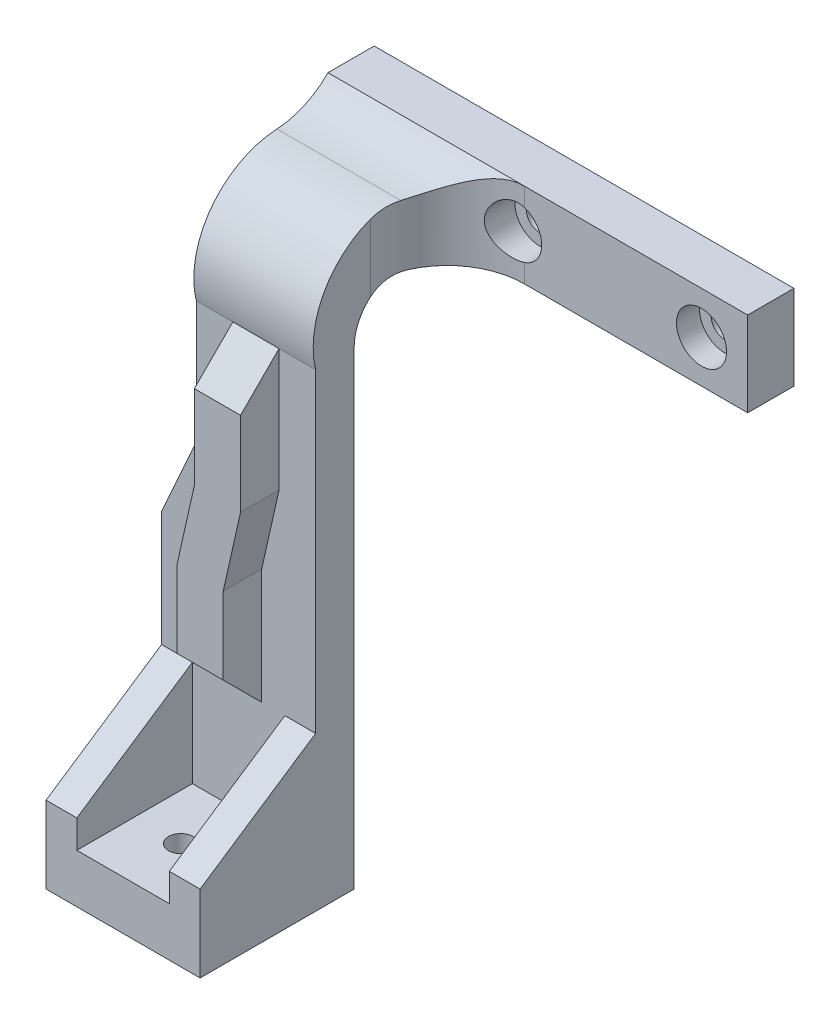
SolidWorks part; units mm, degrees
ref_plane "Plano frontal" through (0, 0, 0) normal (0, 0, 1) x (1, 0, 0)
ref_plane "Plano superior" through (0, 0, 0) normal (0, 1, 0) x (1, 0, 0)
ref_plane "Plano direito" through (0, 0, 0) normal (1, 0, 0) x (0, 0, -1)
sketch "Esboço2" plane through (0, 0, 0) normal (0, 0, 1) x (1, 0, 0)
  line L0 (0, 0) -> (0, -60.9)
  line L1 (0, -60.9) -> (-20, -60.9)
  line L2 (-20, -60.9) -> (-20, -25.9)
  line L3 (-20, -25.9) -> (-15.5, -15.9)
  line L4 (-15.5, -15.9) -> (-15.5, 0)
  line L5 (-15.5, 0) -> (0, 0)
  dimension "D1" = 15.5
  dimension "D2" = 60.9
  dimension "D3" = 35
  dimension "D4" = 15.9
  dimension "D5" = 20
extrude "Ressalto-extrusão1" add sketch "Esboço2" along normal blind 5
sketch "Esboço3" plane through (0, 0, 0) normal (1, 0, 0) x (0, 0, -1)
  line L0 (-5, 0) -> (0, 0)
  line L1 (6.1023, 6.1) -> (6.1023, 14.1) construction
  line L2 (6.1023, 6.1) -> (30.1023, 6.1)
  line L3 (6.1023, 14.1) -> (50.2046, 14.1)
  line L4 (45.2046, -9.0023) -> (45.2046, -60.9)
  line L5 (45.2046, -60.9) -> (50.2046, -60.9)
  line L6 (50.2046, -60.9) -> (50.2046, 14.1)
  arc A0 (6.1023, 6.1) -> (0, 0) centre (6.1023, -0.0023) ccw
  arc A1 (6.1023, 14.1) -> (-5, 0) centre (6.1018, 2.6794) ccw
  arc A2 (45.2046, -9.0029) -> (30.1016, 6.1) centre (30.1016, -9.0029) ccw
extrude "Ressalto-extrusão2" add sketch "Esboço3" against normal up to surface (15.5 mm away) up to face at (-15.5, -7.95, 2.5)
sketch "Esboço4" plane through (-15.5, 0, 0) normal (-1, 0, 0) x (0, 0, 1)
  line L0 (-50.2046, -60.9) -> (-50.2046, -40.9)
  line L2 (-50.2046, -40.9) -> (-65.2046, -50.9)
  line L3 (-65.2046, -50.9) -> (-65.2046, -60.9)
  line L4 (-65.2046, -60.9) -> (-65.2046, -50.9) construction
  line L5 (-65.2046, -60.9) -> (-50.2046, -40.9) construction
  line L6 (-65.2046, -60.9) -> (-50.2046, -60.9)
  line L13 (-50.2046, 14.1) -> (-50.2046, -60.9) construction
  dimension "D1" = 20
extrude "Ressalto-extrusão3" add sketch "Esboço4" against normal up to surface (15.5 mm away) up to face at (0, -18.647, -20.1425)
sketch "Esboço5" plane through (-20, 0, 0) normal (-1, 0, 0) x (0, 0, 1)
  line L0 (5, -60.9) -> (20, -60.9)
  line L1 (20, -60.9) -> (20, -50.9)
  line L2 (20, -50.9) -> (5, -40.9)
  line L3 (5, -25.9) -> (5, -60.9) construction
  line L4 (5, -40.9) -> (20, -50.9) construction
  line L5 (5, -40.9) -> (5, -60.9)
extrude "Ressalto-extrusão4" add sketch "Esboço5" against normal up to surface (20 mm away) up to face at (0, -22.8397, -27.0751)
sketch "Esboço6" plane through (-15.5, 0, 0) normal (-1, 0, 0) x (0, 0, 1)
  line L5 (-50.2046, -44.0023) -> (-45.2046, -44.0023)
  line L6 (-50.2046, -44.0023) -> (-50.2046, -60.9)
  line L7 (-50.2046, -60.9) -> (-45.2046, -60.9)
  line L8 (-45.2046, -44.0023) -> (-45.2046, -60.9)
extrude "Ressalto-extrusão5" add sketch "Esboço6" along normal blind 23.2
sketch "Esboço7" plane through (0, 0, -45.2046) normal (0, 0, 1) x (1, 0, 0)
  line L0 (-25.2, -44.0023) -> (-25.2, -60.9) construction
  line L1 (-38.7, -44.0023) -> (-25.2, -44.0023)
  line L2 (-38.7, -44.0023) -> (-38.7, -60.9)
  line L3 (-38.7, -60.9) -> (-25.2, -60.9)
  line L4 (-25.2, -44.0023) -> (-25.2, -60.9)
  line L5 (-38.7, -60.9) -> (0, -60.9) construction
extrude "Ressalto-extrusão6" add sketch "Esboço7" along normal blind 8
sketch "Esboço8" plane through (-15.5, 0, 0) normal (-1, 0, 0) x (0, 0, 1)
  line L1 (-45.2046, -9.0023) -> (-47.2046, -9.0023)
  line L2 (-45.2046, -9.0023) -> (-45.2046, -15.5904)
  line L3 (-45.2046, -15.5904) -> (-47.2046, -15.5904)
  line L4 (-47.2046, -9.0023) -> (-47.2046, -15.5904)
extrude "Corte-extrusão1" cut sketch "Esboço8" against normal through all
chamfer "Chanfro2" distance 9 angle 45 1 edges at (-15.5, -44.0023, -47.7046)
sketch "Esboço10" plane through (-15.5, 0, 0) normal (-1, 0, 0) x (0, 0, 1)
  line L0 (-50.2046, -40.9) -> (-50.2046, -60.9)
  line L1 (-50.2046, -60.9) -> (-65.2046, -60.9)
  line L2 (-65.2046, -60.9) -> (-65.2046, -50.9)
  line L3 (-65.2046, -50.9) -> (-50.2046, -40.9)
  dimension "D1" = 20
extrude "Ressalto-extrusão8" add sketch "Esboço10" along normal blind 4.5
sketch "Esboço9" plane through (0, -60.9, 0) normal (0, -1, 0) x (1, 0, 0)
  line L0 (-38.7, -50.2046) -> (-38.7, -53.2046)
  line L1 (-38.7, -53.2046) -> (-20, -59.2046)
  line L5 (-20, -65.2046) -> (-20, -50.2046) construction
  line L6 (-20, -59.2046) -> (-38.7, -53.2046) construction
  line L7 (-38.7, -50.2046) -> (-20, -50.2046)
  line L8 (-20, -50.2046) -> (-20, -59.2046)
extrude "Ressalto-extrusão7" add sketch "Esboço9" against normal blind 6 from offset 5.5 offset against normal yes
sketch "Esboço11" plane through (0, 0, 5) normal (0, 0, 1) x (1, 0, 0)
  line L0 (0, -40.9) -> (-20, -40.9) construction
  line L1 (-16, -40.9) -> (-4, -40.9)
  line L2 (-16, -40.9) -> (-16, -54.5408)
  line L3 (-16, -54.5408) -> (-4, -54.5408)
  line L4 (-4, -40.9) -> (-4, -54.5408)
  line L5 (-16, -50.9) -> (-16, -40.9) construction
extrude "Corte-extrusão2" cut sketch "Esboço11" along normal up to surface up to face at (-10, -45.9, 12.5)
sketch "Esboço13" plane through (0, -60.9, 0) normal (0, -1, 0) x (1, 0, 0)
  line L0 (0, 20) -> (-20, 20) construction
  line L1 (0, -65.2046) -> (-20, -65.2046) construction
  line L2 (0, -45.2046) -> (0, -65.2046) construction
  circle A0 centre (-10, 12.5) radius 1.6
  circle A1 centre (-9.7, -57.7046) radius 1.6
  point P5 (-10, 20)
  dimension "D1" = 3.2
  dimension "D3" = 3.2
  dimension "D2" = 7.5
  dimension "D4" = 9.7
  dimension "D5" = 7.5
extrude "Corte-extrusão4" cut sketch "Esboço13" against normal up to next
sketch "Esboço14" plane through (0, 0, 5) normal (0, 0, 1) x (1, 0, 0)
  line L0 (0, 0) -> (-15.5, 0) construction
  line L1 (-10.75, 0) -> (-4.75, 0)
  line L2 (-10.75, 0) -> (-10.75, -15.9)
  line L4 (-4.75, 0) -> (-4.75, -15.9)
  line L6 (-13, -40.9) -> (-7, -40.9)
  line L7 (-16, -54.5408) -> (-4, -54.5408) construction
  line L8 (0, -40.9) -> (-4, -40.9) construction
  line L9 (-10.75, -15.9) -> (-13, -25.9)
  line L10 (-13, -25.9) -> (-13, -40.9)
  line L11 (-7, -40.9) -> (-7, -25.9)
  line L12 (-7, -25.9) -> (-4.75, -15.9)
  point P6 (-7.75, 0)
  point P7 (-7.75, 0)
  point P11 (-10, -54.5408)
  point P14 (-10, -40.9)
  dimension "D1" = 6
  dimension "D2" = 6
extrude "Ressalto-extrusão9" add sketch "Esboço14" along normal blind 5
sketch "Esboço16" plane through (0, 0, -50.2046) normal (0, 0, -1) x (-1, 0, 0)
  line L0 (0, -40.9) -> (15.5, -40.9) construction
  line L1 (15.5009, -54.5427) -> (4, -54.5427)
  line L2 (15.5009, -54.5427) -> (15.5009, -40.9)
  line L3 (15.5009, -40.9) -> (4, -40.9)
  line L4 (4, -54.5427) -> (4, -40.9)
  line L5 (0, -50.9) -> (4, -40.9) construction
extrude "Corte-extrusão5" cut sketch "Esboço16" along normal through all
sketch "Esboço17" plane through (0, 0, -50.2046) normal (0, 0, -1) x (-1, 0, 0)
  line L0 (6.7505, -40.9) -> (12.7505, -40.9)
  line L2 (12.7505, -40.9) -> (12.7505, 8.1)
  line L3 (12.7505, 8.1) -> (6.7505, 8.1)
  line L4 (6.7505, 8.1) -> (6.7505, -40.9)
  line L5 (4, -54.5427) -> (15.5009, -54.5427) construction
  line L6 (0, -40.9) -> (4, -40.9) construction
  line L7 (15.5, 14.1) -> (0, 14.1) construction
  point P6 (9.7505, -54.5427)
  point P7 (9.7505, -40.9)
  dimension "D1" = 6
  dimension "D2" = 6
extrude "Ressalto-extrusão11" add sketch "Esboço17" along normal blind 5
chamfer "Chanfro3" distance 5 angle 45 4 edges at (-9.7505, -40.9, -55.2046) (-9.7505, 8.1, -55.2046) (-10, -40.9, 10) (-7.75, 0, 10)
sketch "Esboço18" plane through (0, 0, 0) normal (1, 0, 0) x (0, 0, -1)
  line L5 (6.1023, 6.1) -> (30.1023, 6.1) construction
  line L6 (18.1023, 6.1) -> (50.2046, 6.1)
  line L7 (18.1023, 6.1) -> (18.1023, 17.1)
  line L8 (18.1023, 17.1) -> (50.2046, 17.1)
  line L9 (50.2046, 6.1) -> (50.2046, 17.1)
  line L10 (50.2046, -40.9) -> (50.2046, 14.1) construction
  line L11 (6.1023, 14.1) -> (50.2046, 14.1) construction
  dimension "D1" = 3
extrude "Ressalto-extrusão13" add sketch "Esboço18" along normal blind 62 and the other way up to surface
sketch "Esboço19" plane through (0, 0, -50.2046) normal (0, 0, -1) x (-1, 0, 0)
  line L0 (15.5, 17.1) -> (-62, 17.1) construction
  line L1 (6.7505, 17.1) -> (-62, 17.1)
  line L2 (6.7505, 17.1) -> (6.7505, -32.4)
  line L3 (6.7505, -32.4) -> (-62, -32.4)
  line L4 (-62, 17.1) -> (-62, -32.4)
  line L5 (6.7505, 3.1) -> (6.7505, -35.9) construction
  line L6 (-62, 6.1) -> (-62, 17.1) construction
  line L7 (-58, 13.1) -> (-58, 17.1) construction
  line L12 (-58, 13.1) -> (2.7505, 13.1)
  line L13 (-58, 13.1) -> (-58, -28.4)
  line L14 (-58, -28.4) -> (2.7505, -28.4)
  line L15 (2.7505, 13.1) -> (2.7505, -28.4)
  line L16 (-58, 13.1) -> (-62, 13.1) construction
  line L17 (2.7505, 13.1) -> (2.7505, 17.1) construction
  line L18 (2.7505, 13.1) -> (6.7505, 13.1) construction
  line L19 (-58, -28.4) -> (-58, -32.4) construction
  dimension "D1" = 41.5
  dimension "D2" = 4
extrude "Ressalto-extrusão14" add sketch "Esboço19" along normal blind 3
sketch "Esboço21" plane through (0, 0, 0) normal (1, 0, 0) x (0, 0, -1)
  line L0 (18.1023, 6.1) -> (50.2046, 6.1) construction
  line L1 (50.2046, -32.4) -> (47.2046, -32.4)
  line L2 (50.2046, -32.4) -> (50.2046, 6.1)
  line L3 (50.2046, 6.1) -> (47.2046, 6.1)
  line L4 (47.2046, -32.4) -> (47.2046, 6.1)
  line L5 (47.2046, -9.0023) -> (47.2046, -15.5904) construction
extrude "Ressalto-extrusão15" add sketch "Esboço21" along normal up to surface (62 mm away)
sketch "Esboço23" plane through (0, 0, -53.2046) normal (0, 0, -1) x (-1, 0, 0)
  line L1 (-62, 17.1) -> (-62, -32.4) construction
  line L3 (-58, 9.1) -> (-58, 13.1)
  line L4 (-58, 13.1) -> (2.7505, 13.1)
  line L5 (2.7505, 13.1) -> (2.7505, 9.1)
  line L6 (2.7505, -28.4) -> (2.7505, 13.1) construction
  line L8 (6.7505, 9.1) -> (6.7505, 17.1)
  line L9 (6.7505, 17.1) -> (-62, 17.1) construction
  line L10 (6.7505, 5.1) -> (6.7505, 17.1) construction
  line L11 (6.7505, 17.1) -> (-62, 17.1)
  line L12 (-62, 17.1) -> (-62, 9.1)
  line L13 (-62, -7.65) -> (6.7505, -7.65) construction
  line L14 (6.7505, 3.1) -> (6.7505, -35.9) construction
  line L15 (-62, -32.4) -> (-62, -24.4)
  line L16 (6.7505, -32.4) -> (-62, -32.4)
  line L17 (6.7505, -24.4) -> (6.7505, -32.4)
  line L18 (2.7505, -24.4) -> (6.7505, -24.4)
  line L19 (2.7505, -28.4) -> (2.7505, -24.4)
  line L20 (-58, -28.4) -> (2.7505, -28.4)
  line L21 (-58, -24.4) -> (-58, -28.4)
  line L22 (-62, -24.4) -> (-58, -24.4)
  line L23 (-58, 13.1) -> (-58, -28.4) construction
  line L24 (-62, 9.1) -> (-58, 9.1)
  line L25 (2.7505, 9.1) -> (6.7505, 9.1)
  dimension "D1" = 8
extrude "Ressalto-extrusão17" add sketch "Esboço23" along normal blind 15.5
sketch "Esboço25" plane through (0, 0, -68.7046) normal (0, 0, -1) x (-1, 0, 0)
  line L2 (-62, 17.1) -> (-62, 9.1)
  line L3 (-27.6248, 13.1) -> (-27.6248, -28.4) construction
  line L5 (2.7505, -28.4) -> (-58, -28.4) construction
  line L8 (-62, 17.1) -> (-62, 9.1) construction
  line L10 (-64, 17.1) -> (-62, 17.1)
  line L14 (-58, -7.65) -> (2.7505, -7.65) construction
  line L15 (-58, 9.1) -> (-58, -24.4) construction
  line L16 (2.7505, -24.4) -> (2.7505, 9.1) construction
  line L23 (6.7505, 17.1) -> (-62, 17.1) construction
  line L24 (-64, 9.1) -> (-62, 9.1)
  line L25 (-58, 13.1) -> (2.7505, 13.1) construction
  line L26 (8.7505, 9.1) -> (6.7505, 9.1)
  line L27 (8.7505, 17.1) -> (6.7505, 17.1)
  line L28 (6.7505, 17.1) -> (6.7505, 9.1)
  line L29 (6.7505, -32.4) -> (6.7505, -24.4)
  line L30 (8.7505, -32.4) -> (6.7505, -32.4)
  line L31 (8.7505, -24.4) -> (6.7505, -24.4)
  line L32 (-64, -24.4) -> (-62, -24.4)
  line L33 (-64, -32.4) -> (-62, -32.4)
  line L34 (-62, -32.4) -> (-62, -24.4)
  arc A4 (-64, 17.1) -> (-64, 9.1) centre (-64, 13.1) ccw
  arc A8 (8.7505, 17.1) -> (8.7505, 9.1) centre (8.7505, 13.1) cw
  arc A9 (8.7505, -32.4) -> (8.7505, -24.4) centre (8.7505, -28.4) ccw
  arc A10 (-64, -32.4) -> (-64, -24.4) centre (-64, -28.4) cw
  dimension "D1" = 8
  dimension "D2" = 2
extrude "Ressalto-extrusão18" add sketch "Esboço25" against normal up to surface (18.5 mm away) up to face at (-14.0669, -31.7426, -50.2046)
sketch "Esboço26" plane through (0, 0, -68.7046) normal (0, 0, -1) x (-1, 0, 0)
  line L0 (-27.6248, 13.1) -> (-27.6248, -28.4) construction
  line L1 (-58, 13.1) -> (2.7505, 13.1) construction
  line L2 (2.7505, -28.4) -> (-58, -28.4) construction
  line L4 (-58, 9.1) -> (-58, -24.4) construction
  line L5 (-58, -7.65) -> (2.7505, -7.65) construction
  line L6 (2.7505, -24.4) -> (2.7505, 9.1) construction
  circle A4 centre (-64, 13.1) radius 1.8
  circle A8 centre (8.7505, 13.1) radius 1.8
  circle A9 centre (8.7505, -28.4) radius 1.8
  circle A10 centre (-64, -28.4) radius 1.8
  dimension "D1" = 3.6
extrude "Corte-extrusão7" cut sketch "Esboço26" against normal blind 6
sketch "Esboço27" plane through (62, 0, 0) normal (1, 0, 0) x (0, 0, -1)
  line L1 (18.1023, 17.1) -> (47.2046, 17.1)
  line L2 (18.1023, 17.1) -> (18.1023, 6.1)
  line L3 (18.1023, 6.1) -> (47.2046, 6.1)
  line L4 (47.2046, 17.1) -> (47.2046, 6.1)
extrude "Corte-extrusão8" cut sketch "Esboço27" against normal blind 20.5
sketch "Esboço29" plane through (41.5, 0, 0) normal (1, 0, 0) x (0, 0, -1)
  line L0 (24.1023, 17.1) -> (22.4864, 13.1005)
  line L1 (47.2046, 17.1) -> (18.1023, 17.1) construction
  line L2 (22.4864, 13.1005) -> (18.1023, 13.1005)
  line L3 (18.1023, 17.1) -> (18.1023, 6.1) construction
  line L4 (18.1023, 13.1005) -> (18.1023, 17.1)
  line L5 (18.1023, 17.1) -> (24.1023, 17.1)
  line L7 (18.1023, 6.1) -> (47.2046, 6.1) construction
  circle A0 centre (22.3646, 9.5242) radius 1.9
  dimension "D4" = 3.8
  dimension "D1" = 6
  dimension "D2" = 3.9995
  dimension "D3" = 112
  dimension "D5" = 4.2623
  dimension "D6" = 3.4242
extrude "Corte-extrusão9" cut sketch "Esboço29" against normal blind 2.5
sketch "Esboço22" plane through (0, 0, 0) normal (1, 0, 0) x (0, 0, -1)
  line L0 (45.2046, -9.0029) -> (47.2046, -9.0023)
  line L1 (47.2046, -32.4) -> (47.2046, 17.1) construction
  line L2 (45.2046, -9.0023) -> (47.2046, -9.0023) construction
  line L3 (47.2046, -9.0023) -> (47.2046, 6.1)
  line L4 (47.2046, 6.1) -> (30.1016, 6.1)
  arc A0 (45.2046, -9.0029) -> (30.1016, 6.1) centre (30.1016, -9.0029) ccw
  arc A1 (45.2046, -9.0023) -> (30.1023, 6.1) centre (30.1016, -9.0029) ccw construction
extrude "Ressalto-extrusão20" add sketch "Esboço22" against normal blind 15.5 from surface at 41.5 starting at face at (41.5, 12.1002, -29.5337)
sketch "Esboço30" plane through (0, 17.1, 0) normal (0, 1, 0) x (1, 0, 0)
  circle A0 centre (-10.5, 22.6023) radius 1.9
  circle A1 centre (24.5, 22.6023) radius 1.9
  dimension "D1" = 3.8
extrude "Corte-extrusão10" cut sketch "Esboço30" against normal blind 6
sketch "Esboço32" plane through (0, 0, -18.1023) normal (0, 0, 1) x (1, 0, 0)
  line L6 (-38.7, -60.9) -> (69.8062, -60.9)
  line L7 (-38.7, -60.9) -> (-38.7, 18.9828)
  line L8 (-38.7, 18.9828) -> (69.8062, 18.9828)
  line L9 (69.8062, -60.9) -> (69.8062, 18.9828)
extrude "Corte-extrusão11" cut sketch "Esboço32" against normal through all
sketch "Esboço33" plane through (0, 0, -18.1023) normal (0, 0, -1) x (-1, 0, 0)
  line L1 (15.5, 6.1) -> (-39, 6.1)
  line L2 (15.5, 6.1) -> (15.5, 17.1)
  line L3 (15.5, 17.1) -> (-39, 17.1)
  line L4 (-39, 6.1) -> (-39, 17.1)
extrude "Ressalto-extrusão21" add sketch "Esboço33" against normal blind 6
sketch "Esboço34" plane through (0, 0, -18.1023) normal (0, 0, -1) x (-1, 0, 0)
  line L1 (15.5, 6.1) -> (15.5, 17.1) construction
  line L2 (-39, 17.1) -> (-39, 6.1) construction
  line L4 (0, 6.1) -> (0, 0) construction
  circle A1 centre (-33, 11.6) radius 1.75
  circle A2 centre (-9, 11.6) radius 1.75
  point P8 (15.5, 11.6)
  dimension "D1" = 3.5
  dimension "D2" = 6
  dimension "D3" = 9
extrude "Corte-extrusão12" cut sketch "Esboço34" against normal up to next
sketch "Esboço35" plane through (0, 0, -12.1023) normal (0, 0, 1) x (1, 0, 0)
  circle A0 centre (9, 11.6) radius 3.25
  circle A1 centre (33, 11.6) radius 3.25
  dimension "D1" = 6.5
extrude "Corte-extrusão13" cut sketch "Esboço35" against normal blind 3
fillet "Filete1" radius 10 2 edges at (0, 10.1, -12.1023) (-7.75, 14.1, -12.1023)
